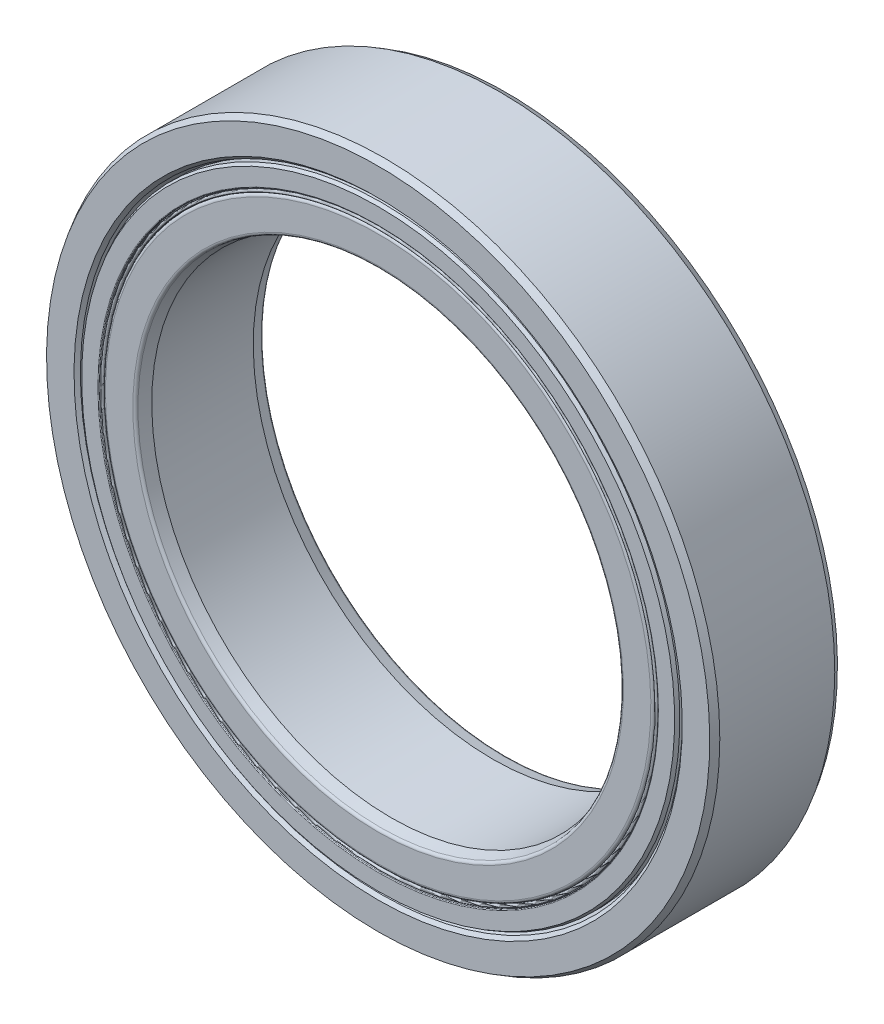
SolidWorks part; units mm, degrees
ref_plane "Front Plane" through (0, 0, 0) normal (0, 0, 1) x (1, 0, 0)
ref_plane "Top Plane" through (0, 0, 0) normal (0, 1, 0) x (1, 0, 0)
ref_plane "Right Plane" through (0, 0, 0) normal (1, 0, 0) x (0, 0, -1)
sketch "Sketch1" plane through (0, 0, 0) normal (0, 0, 1) x (1, 0, 0)
  line L0 (-10.5, 0) -> (10.5, 0) construction
  line L1 (-7.5, 0) -> (7.5, 0) construction
  circle A0 centre (0, 0) radius 7.5 construction
  circle A1 centre (0, 0) radius 10.5 construction
  point P3 (0, 0)
  point P6 (0, 0)
  point P7 (0, -7.5)
  point P11 (0, -10.5)
  point P12 (0, 7.5)
  point P13 (0, 10.5)
  dimension "OD" = 21
  dimension "ID" = 15
sketch "Sketch2" plane through (0, 0, 0) normal (1, 0, 0) x (0, 0, -1)
  line L0 (-2, 10.5) -> (2, 10.5) construction
  line L1 (0, 10.5) -> (0, -10.5) construction
  line L2 (1.8, 10.5) -> (-1.8, 10.5)
  line L3 (-1.8, 10.5) -> (-2, 10.3845)
  line L4 (-2, 10.3845) -> (-2, 9.524)
  line L5 (-1.683, 9.345) -> (-1.0675, 9.345)
  line L6 (1.683, 9.345) -> (1.0675, 9.345)
  line L7 (2, 10.3845) -> (2, 9.524)
  line L8 (1.8, 10.5) -> (2, 10.3845)
  line L9 (-1.0675, 9.345) -> (-1.0675, 9.73) construction
  line L10 (-1.0675, 9.73) -> (-1.0675, 10.115) construction
  line L11 (0, 10.5) -> (0, -10.5) construction
  line L12 (-2, 0) -> (2, 0) construction
  line L13 (2, 7.5) -> (-2, 7.5) construction
  line L14 (-2, 7.5) -> (-2, -7.5) construction
  line L15 (-2, -7.5) -> (2, -7.5) construction
  line L16 (2, 10.5) -> (2, -10.5) construction
  line L17 (-1.0675, 10.115) -> (-1.0675, 10.5) construction
  line L18 (-1.0675, 10.115) -> (0, 10.115) construction
  line L20 (-1.683, 9.345) -> (-1.9, 9.424)
  line L21 (-1.9, 9.424) -> (-2, 9.524)
  line L26 (1.9, 9.424) -> (2, 9.524)
  line L27 (1.683, 9.345) -> (1.9, 9.424)
  arc A0 (-1.0675, 9.345) -> (1.0675, 9.345) centre (0, 8.99) cw
  circle A1 centre (0, 8.99) radius 1.125 construction
  point P17 (0, 0)
  point P21 (0, 10.5)
  point P30 (0, -7.5)
  dimension "Approx. Ball Dia." = 2.25
  dimension "Width" = 4
  dimension "For Shaft Diameter" = 15
  dimension "For Housing ID" = 21
  dimension "D4" = 18.69
  dimension "D2" = 20
  dimension "D5" = 45
  dimension "D1" = 30
  dimension "D6" = 0.2
  dimension "D7" = 0.1
sketch "Sketch3" plane through (0, 0, 0) normal (1, 0, 0) x (0, 0, -1)
  line L14 (-1.683, 9.345) -> (-1.9, 9.424) construction
  line L15 (-1.9, 9.424) -> (-2, 9.524) construction
  line L16 (-2, 10.3845) -> (-2, 9.524) construction
  line L17 (-1.8, 10.5) -> (-2, 10.3845) construction
  line L18 (1.8, 10.5) -> (-1.8, 10.5) construction
  line L19 (1.8, 10.5) -> (2, 10.3845) construction
  line L20 (2, 10.3845) -> (2, 9.524) construction
  line L21 (1.9, 9.424) -> (2, 9.524) construction
  line L22 (1.683, 9.345) -> (1.9, 9.424) construction
  line L23 (1.683, 9.345) -> (1.0675, 9.345) construction
  line L24 (-1.683, 9.345) -> (-1.0675, 9.345) construction
  line L25 (-1.683, 9.345) -> (-1.9, 9.424)
  line L26 (-1.9, 9.424) -> (-2, 9.524)
  line L27 (-2, 10.3845) -> (-2, 9.524)
  line L28 (-1.8, 10.5) -> (-2, 10.3845)
  line L29 (1.8, 10.5) -> (-1.8, 10.5)
  line L30 (1.8, 10.5) -> (2, 10.3845)
  line L31 (2, 10.3845) -> (2, 9.524)
  line L32 (1.9, 9.424) -> (2, 9.524)
  line L33 (1.683, 9.345) -> (1.9, 9.424)
  line L34 (1.683, 9.345) -> (1.0675, 9.345)
  line L35 (-1.683, 9.345) -> (-1.0675, 9.345)
  arc A2 (1.0675, 9.345) -> (-1.0675, 9.345) centre (0, 8.99) ccw construction
  arc A3 (1.0675, 9.345) -> (-1.0675, 9.345) centre (0, 8.99) ccw
revolve "Revolve1" add sketch "Sketch3" angle 360 about L12
sketch "Sketch4" plane through (0, 0, 0) normal (1, 0, 0) x (0, 0, -1)
  line L0 (0, 10.5) -> (0, -10.5) construction
  line L1 (0, 10.5) -> (0, -10.5) construction
  line L2 (-1.5894, 7.5) -> (-1.93, 7.5912)
  line L3 (-2, 7.6825) -> (-2, 8.5405)
  line L4 (2, -10.3845) -> (2, 10.3845) construction
  line L5 (-1.9055, 8.635) -> (-1.0675, 8.635)
  line L6 (-1.5894, 7.5) -> (1.5894, 7.5)
  line L7 (2, 10.3845) -> (2, 9.524) construction
  line L8 (1.5894, 7.5) -> (1.93, 7.5912)
  line L9 (0, 10.115) -> (0, 7.5) construction
  line L10 (2, 7.6825) -> (2, 8.5405)
  line L11 (1.9055, 8.635) -> (1.0675, 8.635)
  line L12 (1.5894, 7.5) -> (1.5894, 7.5912) construction
  line L13 (1.5894, 7.5912) -> (1.5894, 7.6825) construction
  line L14 (1.5894, 7.6825) -> (1.5894, 7.7738) construction
  line L15 (1.5894, 7.7738) -> (1.5894, 7.865) construction
  circle A0 centre (0, 8.99) radius 1.125 construction
  arc A1 (1.0675, 8.635) -> (-1.0675, 8.635) centre (0, 8.99) cw
  arc A2 (2, 8.5405) -> (1.9055, 8.635) centre (1.9055, 8.5405) ccw
  arc A3 (-2, 8.5405) -> (-1.9055, 8.635) centre (-1.9055, 8.5405) cw
  arc A4 (1.93, 7.5912) -> (2, 7.6825) centre (1.9055, 7.6825) ccw
  arc A5 (-1.93, 7.5912) -> (-2, 7.6825) centre (-1.9055, 7.6825) cw
  point P14 (2, 7.61)
  point P36 (0, 7.865)
  dimension "D1" = 15
revolve "Revolve2" add sketch "Sketch4" angle 360 about L12
sketch "Sketch5" plane through (0, 0, 0) normal (1, 0, 0) x (0, 0, -1)
  line L0 (-1.125, 8.99) -> (1.125, 8.99)
  arc A2 (-1.125, 8.99) -> (1.125, 8.99) centre (0, 8.99) cw
  arc A3 (1.0675, 9.345) -> (-1.0675, 9.345) centre (0, 8.99) ccw construction
revolve "Revolve3" add sketch "Sketch5" angle 360 about L0
pattern_circular "CirPattern1" count 16 over 360 about axis through (0, 0, 2) along (0, 0, -1) of bodies 104
sketch "Sketch6" plane through (0, 0, 0) normal (1, 0, 0) x (0, 0, -1)
  line L1 (-1.8961, 9.345) -> (-1.125, 9.345)
  line L2 (-2, 9.285) -> (-2, 8.779)
  line L3 (-1.976, 8.755) -> (-1.125, 8.755)
  line L4 (-1.125, 9.345) -> (-1.125, 8.755)
  line L5 (-2, 7.6825) -> (-2, 8.5405) construction
  line L6 (-1.8, 10.5) -> (-2, 10.3845) construction
  line L7 (0, 10.5) -> (0, 7.5) construction
  line L8 (1.976, 8.755) -> (1.125, 8.755)
  line L9 (1.125, 9.345) -> (1.125, 8.755)
  line L10 (1.8961, 9.345) -> (1.125, 9.345)
  line L11 (2, 9.285) -> (2, 8.779)
  line L13 (-1.9055, 8.635) -> (-1.0675, 8.635) construction
  line L14 (-2, 9.285) -> (-1.8961, 9.345)
  line L15 (-1.683, 9.345) -> (-1.0675, 9.345) construction
  line L16 (2, 9.285) -> (1.8961, 9.345)
  arc A0 (-2, 8.779) -> (-1.976, 8.755) centre (-1.976, 8.779) ccw
  circle A1 centre (0, 8.99) radius 1.125 construction
  arc A2 (2, 8.779) -> (1.976, 8.755) centre (1.976, 8.779) cw
  point P26 (-2, 8.755)
  dimension "D3" = 0.024
  dimension "D1" = 0.12
  dimension "D2" = 0.06
revolve "Revolve4" add sketch "Sketch6" angle 360 about L12
sketch "Sketch7" plane through (0, 0, 0) normal (1, 0, 0) x (0, 0, -1)
  line L3 (-1.125, 8.755) -> (-1.9026, 8.755)
  line L4 (-1.976, 8.755) -> (-1.125, 8.755) construction
  line L7 (0, 7.865) -> (0, 7.5) construction
  line L8 (0, 10.5) -> (0, -10.5) construction
  line L21 (-1.9026, 8.755) -> (-1.9322, 8.7498)
  line L22 (-1.93, 8.725) -> (-1.955, 8.725)
  line L23 (-1.955, 8.635) -> (-1.125, 8.635)
  line L24 (-1.125, 8.635) -> (-1.125, 8.755)
  line L25 (-1.9055, 8.635) -> (-1.0675, 8.635) construction
  line L26 (-2, 8.779) -> (-2, 8.635) construction
  line L27 (-2, 8.635) -> (-1.955, 8.635) construction
  line L28 (-1.9026, 8.755) -> (-1.9026, 8.725) construction
  line L29 (-1.9026, 8.725) -> (-1.9026, 8.695) construction
  line L30 (-1.9026, 8.695) -> (-1.9026, 8.665) construction
  line L31 (-1.9026, 8.665) -> (-1.9026, 8.635) construction
  circle A2 centre (0, 8.99) radius 1.125 construction
  arc A9 (-1.9322, 8.7498) -> (-1.93, 8.725) centre (-1.93, 8.7375) ccw
  arc A10 (-1.955, 8.725) -> (-1.955, 8.635) centre (-1.955, 8.68) ccw
  dimension "D1" = 0.025
  dimension "D2" = 10
revolve "Revolve5" add sketch "Sketch7" angle 360 about L12
equation "\"D4@Sketch2\"=\"OD@Sketch1\"*.89"
equation "\"D1@Sketch6\"=(\"OD@Sketch1\"-\"ID@Sketch1\")*.02"
equation "\"D2@Sketch6\"=\"D1@Sketch6\"*.5"
equation "\"D3@Sketch6\"=\"D1@Sketch6\"*.2"
equation "\"D6@Sketch2\"=\"Width@Sketch2\"*.05"
equation "\"D7@Sketch2\"=\"D6@Sketch2\"*.5"
equation "\"D1@CirPattern1\" =  ( pi * \"OD@Sketch1\" )  * .5625 / \"Approx. Ball Dia.@Sketch2\""
equation "\"Approx. Ball Dia.@Sketch2\"=(\"OD@Sketch1\"-\"ID@Sketch1\")*.5*.75"
